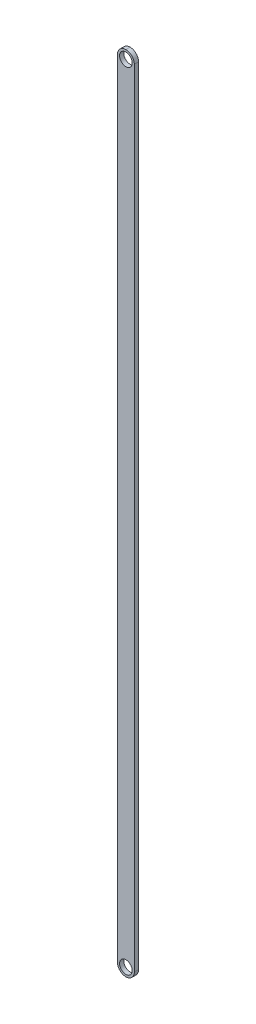
SolidWorks part; units mm, degrees
material "1023 Carbon Steel Sheet (SS)"
ref_plane "Front" through (0, 0, 0) normal (0, 0, 1) x (1, 0, 0)
ref_plane "Top" through (0, 0, 0) normal (0, 1, 0) x (1, 0, 0)
ref_plane "Right" through (0, 0, 0) normal (1, 0, 0) x (0, 0, -1)
sketch "Sketch1" plane through (0, 0, 0) normal (0, 0, 1) x (1, 0, 0)
  line L0 (0, 47.5) -> (0, -47.5) construction
  line L1 (-1, 47.5) -> (1, 47.5)
  line L2 (-1, 47.5) -> (-1, -47.5)
  line L3 (-1, -47.5) -> (1, -47.5)
  line L4 (1, 47.5) -> (1, -47.5)
  line L5 (-1, 47.5) -> (1, -47.5) construction
  line L6 (-1, -47.5) -> (1, 47.5) construction
  circle A0 centre (0, -46.5) radius 0.75
  circle A1 centre (0, 46.5) radius 0.75
  point P0 (0, 0)
  dimension "D3" = 1.5
  dimension "D1" = 2
  dimension "D2" = 95
  dimension "D4" = 1
  dimension "D5" = 1
extrude "Boss-Extrude1" add sketch "Sketch1" along normal blind 0.5
fillet "Fillet1" radius 1 4 edges at (1, -47.5, 0.25) (-1, -47.5, 0.25) (-1, 47.5, 0.25) (1, 47.5, 0.25)
